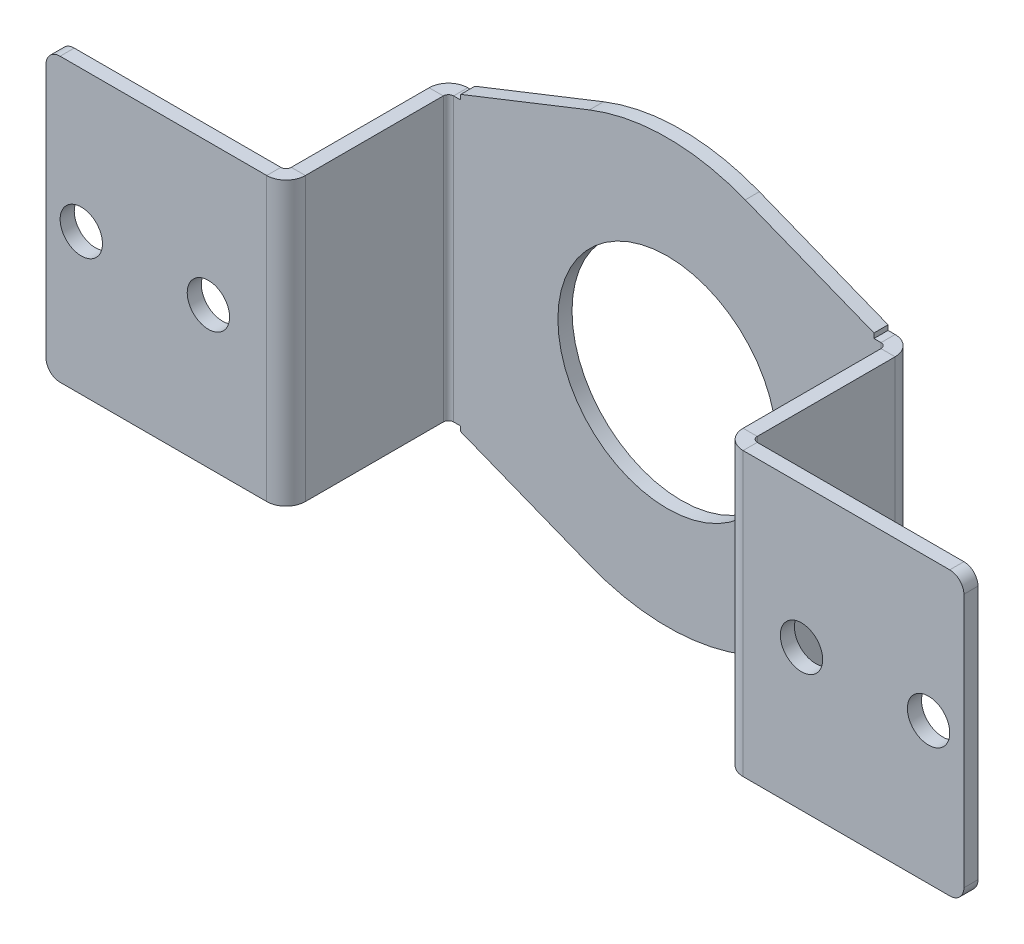
SolidWorks part; units mm, degrees
note: The reader was unsure of these and kept them because the rebuilt part matched: flange length of "Edge-Flange1", "Edge-Flange2".
material "1023 Carbon Steel Sheet (SS)"
ref_plane "Front Plane" through (0, 0, 0) normal (0, 0, 1) x (1, 0, 0)
ref_plane "Top Plane" through (0, 0, 0) normal (0, 1, 0) x (1, 0, 0)
ref_plane "Right Plane" through (0, 0, 0) normal (1, 0, 0) x (0, 0, -1)
sketch "Sketch1" plane through (0, 0, 0) normal (0, 0, 1) x (1, 0, 0)
  line L0 (0, 0) -> (-65, 0) construction
  line L2 (-31, 20) -> (-11.0341, 27.8971)
  line L3 (-31, -20) -> (-11.0341, -27.8971)
  line L4 (-31, 20) -> (-31, -20)
  line L5 (0, 0) -> (0, 30) construction
  line L6 (31, -20) -> (11.0341, -27.8971)
  line L7 (31, 20) -> (31, -20)
  line L8 (31, 20) -> (11.0341, 27.8971)
  circle A0 centre (0, 0) radius 15.5
  arc A1 (-11.0341, -27.8971) -> (11.0341, -27.8971) centre (0, 0) ccw
  arc A2 (11.0341, 27.8971) -> (-11.0341, 27.8971) centre (0, 0) ccw
  point P7 (-65, 0)
  point P13 (-31, 0)
  dimension "D1" = 31
  dimension "D2" = 60
  dimension "D3" = 40
  dimension "D5" = 31
base flange "Base-Flange1" sketch "Sketch1" thickness 2 reverse thickness direction no parameters "D1"=0.7366
edge flange "Edge-Flange1" sketch "Sketch8" flange profiles "Sketch8", "Sketch10" flange angle 90 flange length 23 flange position material outside bend radius 0.7366 thickness 2 relief rectangular parameters "D6"=10, "D8"=1
sketch "Sketch8" plane through (-31, 0, 0) normal (-1, 0, 0) x (0, -1, 0)
  line L2 (-20, 0) -> (-20, 21)
  line L3 (-20, 21) -> (20, 21)
  line L4 (20, 21) -> (20, 0)
  line L7 (-20, 0) -> (20, 0) construction
  line L8 (-20, 0) -> (20, 0)
sketch "Sketch10" plane through (31, 0, 0) normal (1, 0, 0) x (0, 1, 0)
  line L0 (-20, 0) -> (20, 0) construction
  line L1 (-20, 0) -> (20, 0)
  line L2 (-20, 0) -> (-20, 21)
  line L3 (-20, 21) -> (20, 21)
  line L4 (20, 21) -> (20, 0)
bend "EdgeBend1" bend radius 0.7366 bend angle 90 parameters "D5"=1
bend "EdgeBend2" bend radius 0.7366 bend angle 90 parameters "D5"=3
edge flange "Edge-Flange2" sketch "Sketch15" flange profiles "Sketch15", "Sketch16" flange angle 90 flange length 34 flange position material outside bend radius 0.7366 thickness 2 relief rectangular parameters "D6"=10, "D8"=1
sketch "Sketch15" plane through (-33, 0, 21) normal (0, 0, 1) x (0, 1, 0)
  line L2 (-20, 0) -> (-20, 32)
  line L3 (-20, 32) -> (20, 32)
  line L4 (20, 32) -> (20, 0)
  line L7 (-20, 0) -> (20, 0) construction
  line L8 (-20, 0) -> (20, 0)
sketch "Sketch16" plane through (33, 0, 21) normal (0, 0, 1) x (0, -1, 0)
  line L0 (-20, 0) -> (20, 0) construction
  line L1 (-20, 0) -> (20, 0)
  line L2 (-20, 0) -> (-20, 32)
  line L3 (-20, 32) -> (20, 32)
  line L4 (20, 32) -> (20, 0)
bend "EdgeBend3" bend radius 0.7366 bend angle 90 parameters "D5"=4
bend "EdgeBend4" bend radius 0.7366 bend angle 90 parameters "D5"=5
sketch "Sketch17" plane through (0, 0, 21) normal (0, 0, -1) x (-1, 0, 0)
  circle A1 centre (60, 0) radius 3
  circle A2 centre (42, 0) radius 3
  circle A3 centre (-60, 0) radius 3
  circle A4 centre (-42, 0) radius 3
  dimension "D1" = 6
  dimension "D2" = 6
  dimension "D3" = 42
  dimension "D4" = 60
  dimension "D5" = 42
  dimension "D6" = 60
extrude "Cut-Extrude1" cut sketch "Sketch17" against normal blind 10 normal cut yes
fillet "Fillet1" radius 2 4 edges at (-65, -20, 22) (65, 20, 22) (65, -20, 22) (-65, 20, 22)
sketch "Bend-Lines1" [suppressed] plane through (0, 0, 0) normal (0, 1, 0) x (1, 0, 0)
sketch "Bounding-Box1" [suppressed] plane through (0, 0, 0) normal (0, 1, 0) x (1, 0, 0)
sheet metal parameters "Sheet-Metal1" thickness 2 parameters "D1"=0.7366
flat pattern "Flat-Pattern1" [suppressed]
sketch "Bend-Lines2" plane through (0, 0, 0) normal (0, 1, 0) x (1, 0, 0)
sketch3d "Bounding-Box2" [suppressed]
  line L0 (30.9987, 30.0007, 0) -> (-31.0001, 29.9992, 0) construction
  line L1 (31.0001, -29.9992, 0) -> (-30.9987, -30.0007, 0) construction
  line L2 (30.9987, 30.0007, 0) -> (31.0001, -29.9992, 0) construction
  line L3 (-31.0001, 29.9992, 0) -> (-30.9987, -30.0007, 0) construction
sheet metal parameters "Sheet-Metal2" thickness 2 parameters "D1"=0.7366
flat pattern "Flat-Pattern1"
sketch "Bend-Lines2" plane through (0, 0, 0) normal (0, 0, 1) x (1, 0, 0)
  line L0 (-31.6273, 25.4296) -> (-31.6273, -25.4296) construction
  line L1 (-31.6273, 25.4296) -> (-31.6273, -25.4296) construction
  line L2 (31.6273, -25.4296) -> (31.6273, 25.4296) construction
  line L3 (31.6273, -25.4296) -> (31.6273, 25.4296) construction
sketch3d "Bounding-Box2" [suppressed]
  line L0 (-51.2533, 30.0012, 0) -> (51.2548, 29.9987, 0) construction
  line L1 (-51.2548, -29.9987, 0) -> (51.2533, -30.0012, 0) construction
  line L2 (-51.2533, 30.0012, 0) -> (-51.2548, -29.9987, 0) construction
  line L3 (51.2548, 29.9987, 0) -> (51.2533, -30.0012, 0) construction
bend of the flat pattern "Flatten-<EdgeBend1>1"
bend of the flat pattern "Flatten-<EdgeBend2>1"
sheet metal parameters "Sheet-Metal3" thickness 2 parameters "D1"=0.7366
flat pattern "Flat-Pattern1"
sketch "Bend-Lines2" plane through (0, 0, 0) normal (0, 0, 1) x (1, 0, 0)
  line L0 (-31.6273, 25.4296) -> (-31.6273, -25.4296) construction
  line L1 (-31.6273, 25.4296) -> (-31.6273, -25.4296) construction
  line L2 (31.6273, -25.4296) -> (31.6273, 25.4296) construction
  line L3 (31.6273, -25.4296) -> (31.6273, 25.4296) construction
  line L4 (51.882, -25.4296) -> (51.882, 25.4296) construction
  line L5 (-51.882, 25.4296) -> (-51.882, -25.4296) construction
  line L6 (51.882, -25.4296) -> (51.882, 25.4296) construction
  line L7 (-51.882, 25.4296) -> (-51.882, -25.4296) construction
sketch3d "Bounding-Box2" [suppressed]
  line L0 (-84.508, 30.002, 0) -> (84.5094, 29.998, 0) construction
  line L1 (-84.5094, -29.998, 0) -> (84.508, -30.002, 0) construction
  line L2 (-84.508, 30.002, 0) -> (-84.5094, -29.998, 0) construction
  line L3 (84.5094, 29.998, 0) -> (84.508, -30.002, 0) construction
bend of the flat pattern "Flatten-<EdgeBend1>1"
bend of the flat pattern "Flatten-<EdgeBend2>1"
bend of the flat pattern "Flatten-<EdgeBend3>1"
bend of the flat pattern "Flatten-<EdgeBend4>1"
sheet metal parameters "Sheet-Metal4" thickness 2 parameters "D1"=0.7366
flat pattern "Flat-Pattern1"
sketch "Bend-Lines2" plane through (0, 0, 0) normal (0, 0, 1) x (1, 0, 0)
  line L0 (-31.6273, 20) -> (-31.6273, -20) construction
  line L1 (-31.6273, 20) -> (-31.6273, -20) construction
  line L2 (31.6273, -20) -> (31.6273, 20) construction
  line L3 (31.6273, -20) -> (31.6273, 20) construction
  line L4 (53.882, -20) -> (53.882, 20) construction
  line L5 (-53.882, 20) -> (-53.882, -20) construction
  line L6 (53.882, -20) -> (53.882, 20) construction
  line L7 (-53.882, 20) -> (-53.882, -20) construction
sketch3d "Bounding-Box2" [suppressed]
  line L0 (-86.5093, -30, 0) -> (86.5093, -30, 0) construction
  line L1 (-86.5093, 30, 0) -> (86.5093, 30, 0) construction
  line L2 (-86.5093, -30, 0) -> (-86.5093, 30, 0) construction
  line L3 (86.5093, -30, 0) -> (86.5093, 30, 0) construction
bend of the flat pattern "Flatten-<EdgeBend1>1"
bend of the flat pattern "Flatten-<EdgeBend2>1"
bend of the flat pattern "Flatten-<EdgeBend3>1"
bend of the flat pattern "Flatten-<EdgeBend4>1"
